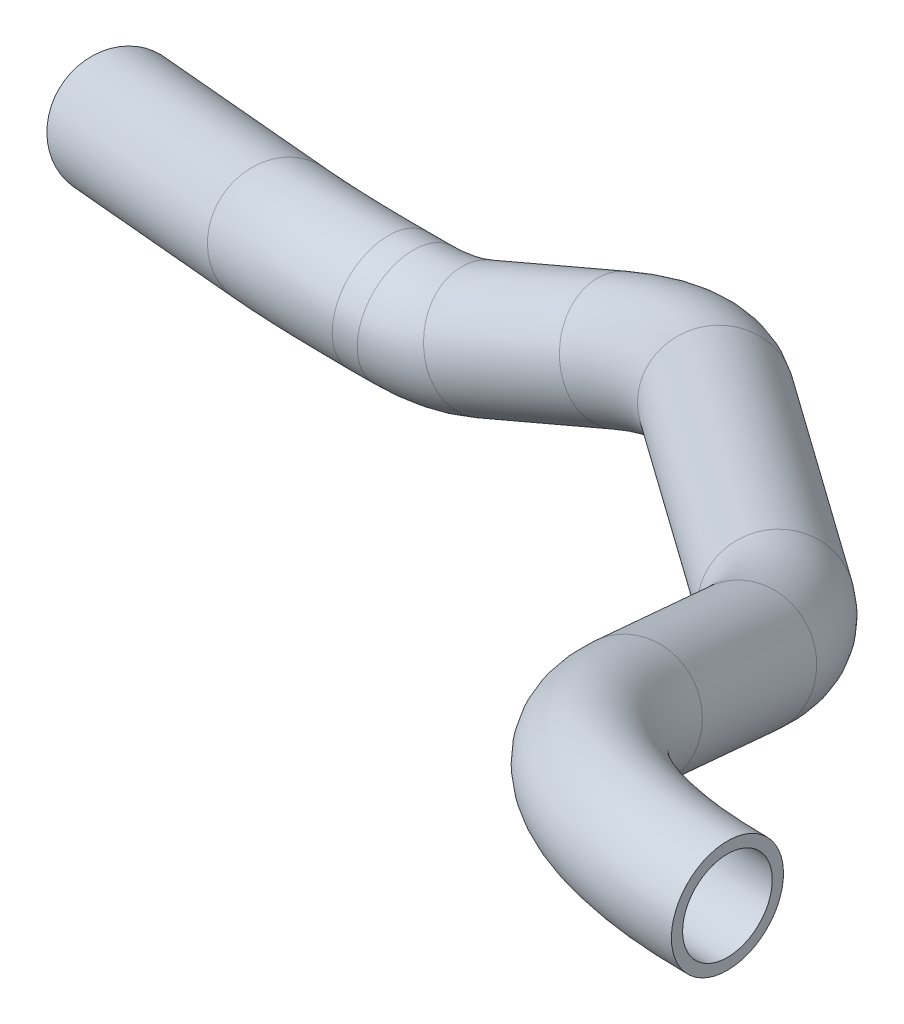
SolidWorks part; units mm, degrees
material "Kauczuk krzemowy"
ref_plane "Płaszczyzna przednia" through (0, 0, 0) normal (0, 0, 1) x (1, 0, 0)
ref_plane "Płaszczyzna górna" through (0, 0, 0) normal (0, 1, 0) x (1, 0, 0)
ref_plane "Płaszczyzna prawa" through (0, 0, 0) normal (1, 0, 0) x (0, 0, -1)
sketch3d "Szkic 3D1"
  line L0 (1151.5519, -307.1135, 173.4396) -> (1185.1562, -297.3574, 185.3468)
  line L1 (1214.309, -293.3269, 190.266) -> (1219.8949, -293.3269, 190.266)
  line L11 (1235.6226, -290.1052, 190.266) -> (1265.9329, -277.1434, 190.266)
  line L12 (1299.9326, -263.5539, 202.6947) -> (1372.473, -237.0602, 261.9242)
  line L15 (1389.581, -226.8029, 286.1194) -> (1403.2764, -210.8228, 325.3058)
  line L22 (1151.5519, -307.1135, 173.4396) -> (1129.6964, -313.4586, 165.6953)
  arc A0 (1372.473, -237.0602, 261.9242) -> (1389.581, -226.8029, 286.1194) centre (1332.5515, -222.2858, 304.2088) ccw
  arc A1 (1185.1562, -297.3574, 185.3468) -> (1214.309, -293.3269, 190.266) centre (1214.309, -337.6911, 136.1197) ccw
  arc A2 (1265.9329, -277.1434, 190.266) -> (1299.9326, -263.5539, 202.6947) centre (1267.5868, -281.0109, 250.1184) ccw
  arc A3 (1235.6226, -290.1052, 190.266) -> (1219.8949, -293.3269, 190.266) centre (1219.8949, -253.3269, 190.266) ccw
  arc A4 (1469.8758, -192.5288, 370.1663) -> (1403.2764, -210.8228, 325.3058) centre (1469.8758, -218.9613, 305.3486) ccw
  point P8 (1199.039, -293.3269, 190.266)
  point P9 (1214.309, -283.5448, 91.7555)
  point P21 (1228.0887, -293.3269, 190.266)
  point P22 (1219.8949, -253.3269, 150.266)
  point P26 (1469.8758, -283.7789, 331.7811)
  point P30 (1384.5798, -232.6385, 271.8094)
  point P31 (1335.0709, -278.0976, 326.0881)
  point P34 (1284.7107, -269.1134, 190.266)
  point P35 (1291.1203, -336.0425, 245.9121)
sweep "Wyciągnięcie po ścieżce-Cienka ścianka1" add path "Szkic 3D1" circular profile diameter 25 parameters "D1"=2.5, "D3"=25
